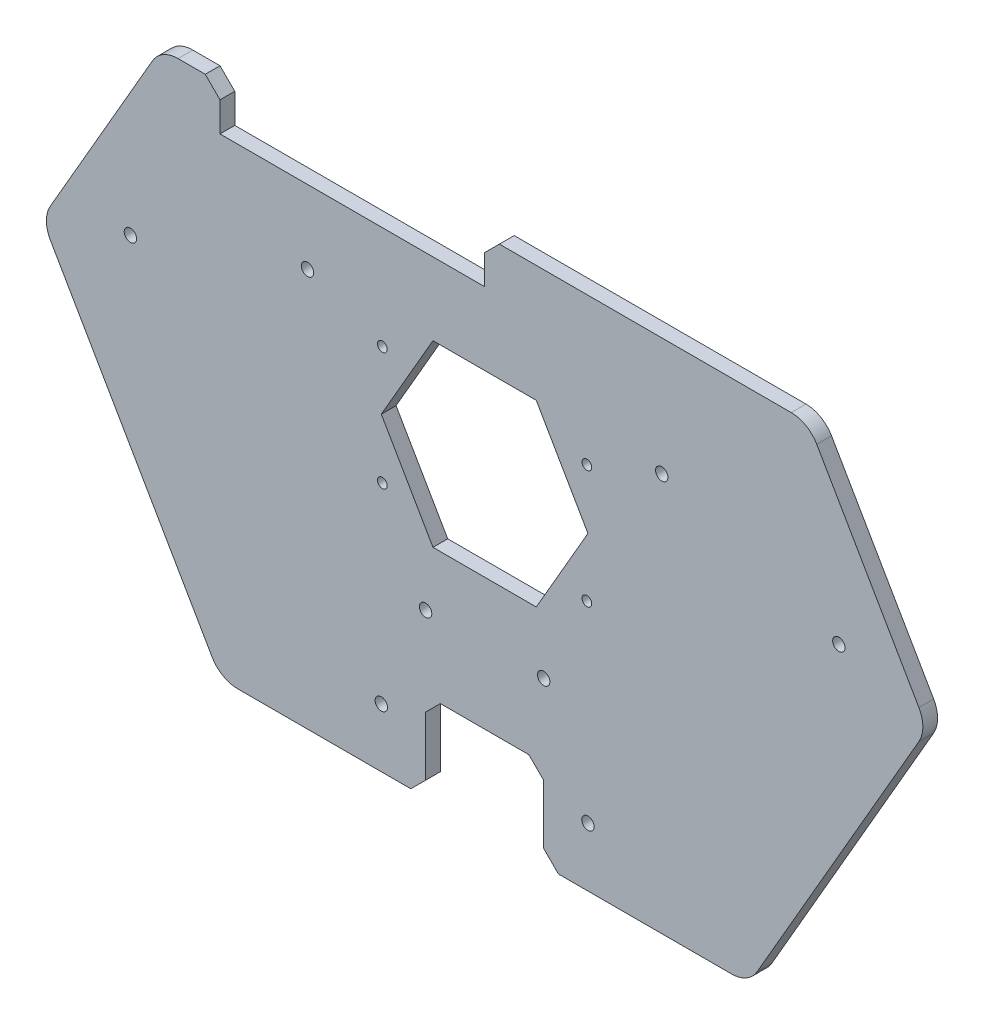
SolidWorks part; units mm, degrees
material "5052-O"
ref_plane "前基準面" through (0, 0, 0) normal (0, 0, 1) x (1, 0, 0)
ref_plane "上基準面" through (0, 0, 0) normal (0, 1, 0) x (1, 0, 0)
ref_plane "右基準面" through (0, 0, 0) normal (1, 0, 0) x (0, 0, -1)
sketch "草圖1" plane through (0, 0, 0) normal (0, 0, 1) x (1, 0, 0)
  line L1 (150, 0) -> (75, 129.9038)
  line L2 (75, 129.9038) -> (-75, 129.9038)
  line L3 (-75, 129.9038) -> (-150, 0)
  line L4 (-150, 0) -> (-75, -129.9038)
  line L5 (-75, -129.9038) -> (75, -129.9038)
  line L6 (75, -129.9038) -> (150, 0)
  circle A0 centre (0, 0) radius 129.9038 construction
  dimension "D1" = 150
extrude "填料-伸長1" add sketch "草圖1" along normal blind 5
ref_axis "基準軸1" through (0, 0, 0) along (0, 0, 1)
sketch "草圖3" plane through (0, 0, 5) normal (0, 0, 1) x (1, 0, 0)
  line L0 (-109.641, 69.9038) -> (-89.641, 69.9038)
  line L1 (-75, 129.9038) -> (-150, 0) construction
  line L2 (-89.641, 69.9038) -> (-89.641, 54.9038)
  line L3 (-89.641, 54.9038) -> (0, 54.9038)
  line L4 (0, 54.9038) -> (0, 69.9038)
  line L5 (0, 69.9038) -> (109.641, 69.9038)
  line L6 (150, 0) -> (75, 129.9038) construction
  line L7 (75, 129.9038) -> (-75, 129.9038) construction
  point P16 (0, 129.9038)
  dimension "D1" = 75
  dimension "D2" = 15
  dimension "D4" = 20
extrude "除料-伸長2" cut sketch "草圖3" against normal through all and the other way through all
sketch "草圖4" plane through (0, 0, 5) normal (0, 0, 1) x (1, 0, 0)
  line L1 (35, 0) -> (17.5, 30.3109)
  line L2 (17.5, 30.3109) -> (-17.5, 30.3109)
  line L3 (-17.5, 30.3109) -> (-35, 0)
  line L4 (-35, 0) -> (-17.5, -30.3109)
  line L5 (-17.5, -30.3109) -> (17.5, -30.3109)
  line L6 (17.5, -30.3109) -> (35, 0)
  circle A0 centre (0, 0) radius 30.3109 construction
  dimension "D1" = 35
extrude "除料-伸長3" cut sketch "草圖4" against normal up to next
chamfer "導角1" distance 5 angle 45 2 edges at (0, 69.9038, 2.5) (-89.641, 69.9038, 2.5)
sketch "草圖5" plane through (0, 0, 5) normal (0, 0, 1) x (1, 0, 0)
  line L0 (-89.4338, -104.9038) -> (-20, -104.9038)
  line L1 (-150, 0) -> (-75, -129.9038) construction
  line L2 (-20, -104.9038) -> (-20, -74.9038)
  line L3 (-20, -74.9038) -> (20, -74.9038)
  line L4 (20, -74.9038) -> (20, -104.9038)
  line L5 (20, -104.9038) -> (89.4338, -104.9038)
  line L6 (75, -129.9038) -> (150, 0) construction
  line L7 (-75, -129.9038) -> (75, -129.9038) construction
  dimension "D1" = 25
  dimension "D2" = 30
  dimension "D3" = 40
extrude "除料-伸長6" cut sketch "草圖5" against normal through all and the other way through all flip side to cut
chamfer "導角2" distance 5 angle 45 4 edges at (20, -104.9038, 2.5) (20, -74.9038, 2.5) (-20, -74.9038, 2.5) (-20, -104.9038, 2.5)
sketch "草圖6" plane through (0, 0, 5) normal (0, 0, 1) x (1, 0, 0)
  circle A0 centre (-35, -85) radius 2.1
  circle A1 centre (-120, 10) radius 2.1
  circle A2 centre (-60, 30) radius 2.1
  circle A3 centre (-20, -50) radius 2.1
  dimension "D1" = 4.2
  dimension "D2" = 4.2
  dimension "D7" = 4.2
  dimension "D8" = 4.2
  dimension "D3" = 35
  dimension "D4" = 85
  dimension "D5" = 120
  dimension "D6" = 10
  dimension "D9" = 50
  dimension "D10" = 20
  dimension "D11" = 30
  dimension "D12" = 60
extrude "除料-伸長7" cut sketch "草圖6" against normal up to next
mirror "鏡射1" about plane through (0, 0, 0) normal (1, 0, 0) of "除料-伸長7"
fillet "圓角1" radius 10 6 edges at (109.641, 69.9038, 2.5) (150, 0, 2.5) (89.4338, -104.9038, 2.5) (-89.4338, -104.9038, 2.5) (-150, 0, 2.5) (-109.641, 69.9038, 2.5)
sketch "草圖8" plane through (0, 0, 5) normal (0, 0, 1) x (1, 0, 0)
  line L0 (-26.25, 15.1554) -> (-34.641, 20) construction
  line L1 (-34.641, 20) -> (34.641, 20) construction
  line L2 (-34.641, 20) -> (-34.641, -20) construction
  line L3 (-34.641, -20) -> (34.641, -20) construction
  line L4 (34.641, 20) -> (34.641, -20) construction
  line L5 (-17.5, 30.3109) -> (-35, 0) construction
  circle A1 centre (0, 0) radius 40 construction
  dimension "D1" = 80
hole_wizard "M4x0.7 螺紋孔1" positions "草圖9" profile "草圖10" tap size "M4x0.7" standard "Ansi Metric"
sketch "草圖9" plane through (0, 0, 5) normal (0, 0, 1) x (1, 0, 0)
  point P0 (-34.641, 20)
  point P3 (34.641, 20)
  point P6 (34.641, -20)
  point P9 (-34.641, -20)
sketch "草圖10" plane through (-34.641, 20, 5) normal (1, 0, 0) x (0, -1, 0)
  line L0 (0, 0) -> (0, 12.4914)
  line L1 (0, 12.4914) -> (1.65, 11.5)
  line L2 (1.65, 11.5) -> (1.65, 0)
  line L5 (1.65, 0) -> (0, 0)
  line L10 (0, 12.4914) -> (-1.65, 11.5) construction
  line L11 (0, -6.35) -> (0, 107.95) construction
  dimension "螺孔鑽直徑" = 3.3
  dimension "螺孔鑽深度" = 11.5
  dimension "導頭角度" = 118
cosmetic thread "鑽孔螺紋1" parameters "D1"=8, "D2"=4
cosmetic thread "鑽孔螺紋2" parameters "D1"=8, "D2"=4
cosmetic thread "鑽孔螺紋3" parameters "D1"=8, "D2"=4
cosmetic thread "鑽孔螺紋4" parameters "D1"=8, "D2"=4
